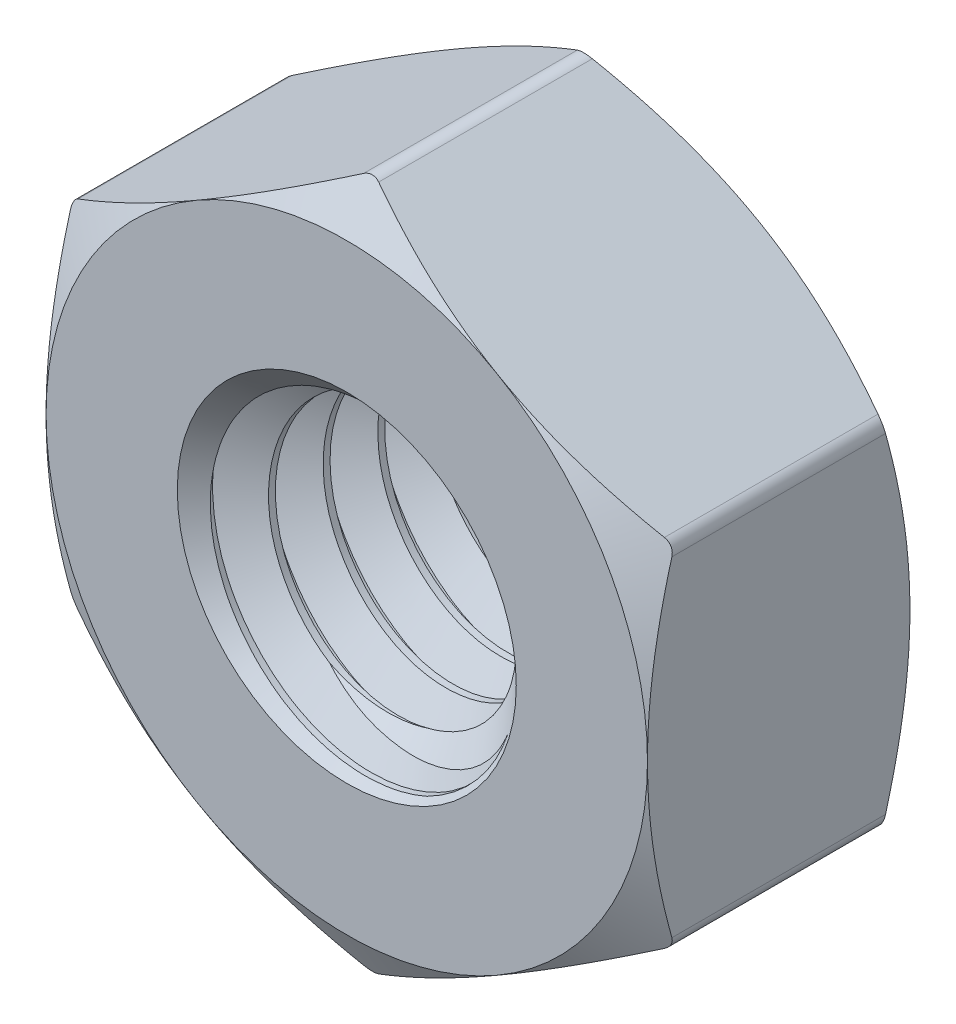
SolidWorks part; units mm, degrees
ref_plane "Front" through (0, 0, 0) normal (0, 0, 1) x (1, 0, 0)
ref_plane "Top" through (0, 0, 0) normal (0, 1, 0) x (1, 0, 0)
ref_plane "Right" through (0, 0, 0) normal (1, 0, 0) x (0, 0, -1)
sketch "Sketch1" plane through (0, 0, 0) normal (0, 0, 1) x (1, 0, 0)
  line L0 (0, 1.5) -> (0, 1) construction
  line L1 (-2.75, 1.5877) -> (-2.75, -1.5877)
  line L2 (-2.75, -1.5877) -> (0, -3.1754)
  line L3 (0, -3.1754) -> (2.75, -1.5877)
  line L4 (2.75, -1.5877) -> (2.75, 1.5877)
  line L5 (2.75, 1.5877) -> (0, 3.1754)
  line L6 (0, 3.1754) -> (-2.75, 1.5877)
  circle A0 centre (0, 0) radius 2.75 construction
  circle A1 centre (0, 0) radius 1.5 construction
  point P10 (0, 1.5)
  dimension "Width" = 5.5
  dimension "Thread Size" = 3
  dimension "Thread Pitch" = 0.5
sketch "Sketch2" plane through (0, 0, 0) normal (1, 0, 0) x (0, 0, -1)
  line L0 (-1.2, 0) -> (1.2, 0) construction
  line L1 (-1.2, 3.1754) -> (1.2, 3.1754) construction
  dimension "Height" = 2.4
sketch "Sketch15" plane through (0, 0, 0) normal (0, 0, 1) x (1, 0, 0)
  line L1 (0, 3.1754) -> (-2.75, 1.5877)
  line L2 (-2.75, 1.5877) -> (-2.75, -1.5877)
  line L3 (-2.75, -1.5877) -> (0, -3.1754)
  line L4 (0, -3.1754) -> (2.75, -1.5877)
  line L5 (2.75, -1.5877) -> (2.75, 1.5877)
  line L6 (2.75, 1.5877) -> (0, 3.1754)
  circle A0 centre (0, 0) radius 2.75 construction
extrude "Boss-Extrude2" add sketch "Sketch15" along normal mid plane 2.4
sketch "Sketch16" plane through (0, 0, 0) normal (0, 0, 1) x (1, 0, 0)
  circle A0 centre (0, 0) radius 1.5 construction
  circle A1 centre (0, 0) radius 1.5
sketch "Sketch4" plane through (0, 0, -1.2) normal (0, 0, -1) x (-1, 0, 0)
  circle A0 centre (0, 0) radius 1.5 construction
  circle A1 centre (0, 0) radius 1.5
extrude "Cut-Extrude4" cut sketch "Sketch16" against normal through all both and the other way through all
sketch "Sketch7" plane through (0, 0, 1.2) normal (0, 0, 1) x (1, 0, 0)
  circle A0 centre (0, 0) radius 2.75 construction
  circle A1 centre (0, 0) radius 2.75
extrude "Cut-Extrude5" cut sketch "Sketch7" against normal through all draft 60 flip side to cut
mirror "Mirror4" about plane through (0, 0, 0) normal (0, 0, 1) of "Cut-Extrude5"
fillet "Fillet2" radius 0.1375 6 edges at (-2.75, 1.5877, 0) (-2.75, -1.5877, 0) (0, -3.1754, 0) (2.75, -1.5877, 0) (2.75, 1.5877, 0) (0, 3.1754, 0)
sketch "Sketch8" plane through (0, 0, 1.2) normal (0, 0, 1) x (1, 0, 0)
  line L0 (0.3882, -1.4489) -> (0, 0) construction
  line L2 (0, 1.5) -> (0, 1) construction
  circle A0 centre (0, 0) radius 1.5 construction
  point P0 (0.3882, -1.4489)
  dimension "D1" = 15
sketch "Sketch13" plane through (0, 0, -1.2) normal (0, 0, -1) x (-1, 0, 0)
  circle A0 centre (0, 0) radius 1.5 construction
  circle A1 centre (0, 0) radius 1.5
extrude "Boss-Extrude1" add sketch "Sketch13" against normal up to surface (2.4 mm away) separate body up to face at (1.5, 0, 1.2)
curve "Helix/Spiral3" pitch 0.5 height 3.4 radius 1.5 centre (0, 0, -1.2) axis (0, 0, 1) start towards (0, 1, 0)
sketch "Sketch12" plane through (0, 0, 0) normal (1, 0, 0) x (0, 0, -1)
  line L0 (1.6375, 1.5) -> (1.2, 1.5)
  line L1 (1.6375, 1.5) -> (1.45, 1.1752)
  line L2 (1.45, 1.1752) -> (1.3875, 1.1752)
  line L3 (1.3875, 1.1752) -> (1.2, 1.5)
  line L4 (1.4188, 1.1752) -> (1.4188, 1.5) construction
  line L5 (1.2938, 1.3376) -> (1.5438, 1.3376) construction
  dimension "D1" = 60
  dimension "D2" = 0.0625
  dimension "D3" = 0.25
sweep "Cut-Sweep1" cut profiles "Sketch12" path "Helix/Spiral3" align with end faces yes
sketch "Sketch17" plane through (0, 0, 1.2) normal (0, 0, 1) x (1, 0, 0)
  circle A1 centre (0, 0) radius 1.5
  circle A2 centre (0, 0) radius 1.5
  dimension "D1" = 0
extrude "Boss-Extrude3" add sketch "Sketch17" against normal up to surface (2.4 mm away) up to face at (1.5, 0, -1.2)
combine bodies "Combine1" operation type subtract main body 127 bodies to subtract 118
sketch "Sketch10" plane through (0, 0, 1.2) normal (0, 0, 1) x (1, 0, 0)
  circle A0 centre (0, 0) radius 1.5 construction
  circle A1 centre (0, 0) radius 1.5 construction
  circle A2 centre (0, 0) radius 1.55
  dimension "D1" = 0.05
extrude "Cut-Extrude2" cut sketch "Sketch10" against normal through all draft 45
sketch "Sketch11" plane through (0, 0, -1.2) normal (0, 0, -1) x (-1, 0, 0)
  circle A1 centre (0, 0) radius 1.55 construction
  circle A2 centre (0, 0) radius 1.55
extrude "Cut-Extrude3" cut sketch "Sketch11" against normal through all draft 45
equation "\"D1\"= \"Height@Sketch2\""
equation "\"D3@Helix/Spiral3\"=\"Height@Sketch2\"+\"Thread Pitch@Sketch1\"*2"
equation "\"D4@Helix/Spiral3\"=\"Thread Pitch@Sketch1\""
equation "\"D2@Sketch12\" = \"D4@Helix/Spiral3\"*.125"
equation "\"D3@Sketch12\" = \"D4@Helix/Spiral3\"*.50"
equation "\"D1@Boss-Extrude2\"=\"Height@Sketch2\""
equation "\"D1@Fillet2\"=\"Width@Sketch1\"*0.025"
equation "\"D1@Sketch10\"=\"Thread Pitch@Sketch1\"*0.1"
